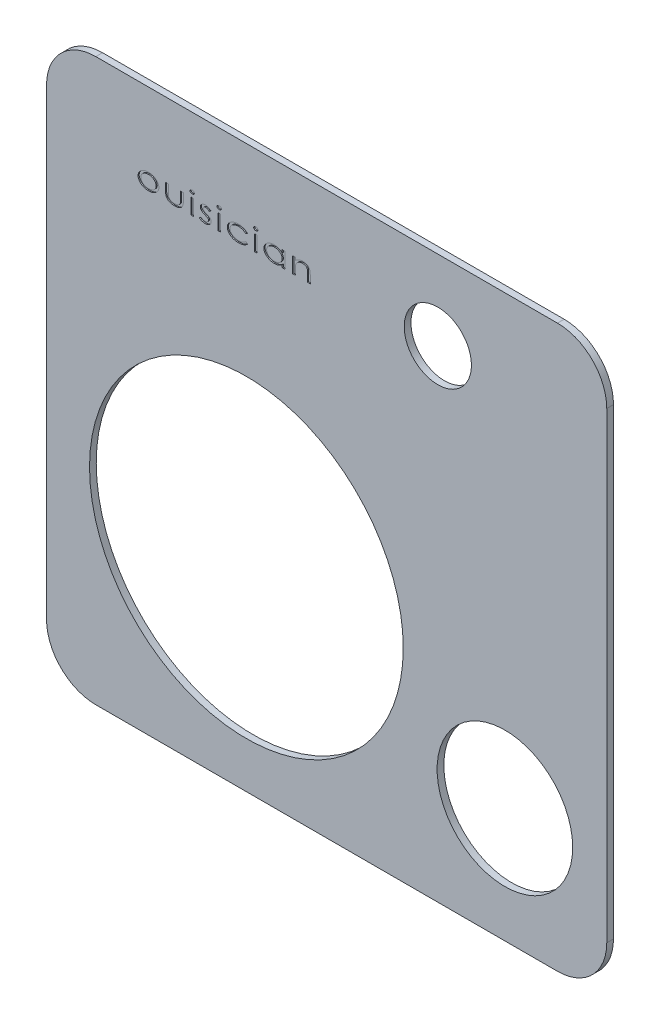
SolidWorks part; units mm, degrees
material "Pine"
ref_plane "Front Plane" through (0, 0, 0) normal (0, 0, 1) x (1, 0, 0)
ref_plane "Top Plane" through (0, 0, 0) normal (0, 1, 0) x (1, 0, 0)
ref_plane "Right Plane" through (0, 0, 0) normal (1, 0, 0) x (0, 0, -1)
sketch "Sketch1" plane through (0, 0, 0) normal (0, 0, 1) x (1, 0, 0)
  line L1 (0, 0) -> (500, 0)
  line L2 (0, 0) -> (0, 501)
  line L3 (0, 501) -> (500, 501)
  line L4 (500, 0) -> (500, 501)
  dimension "D1" = 500
  dimension "D2" = 501
extrude "Boss-Extrude1" add sketch "Sketch1" along normal blind 6
fillet "Fillet1" radius 44 4 edges at (0, 0, 3) (500, 0, 3) (0, 501, 3) (500, 501, 3)
sketch "Sketch2" plane through (0, 0, 6) normal (0, 0, 1) x (1, 0, 0)
  circle A0 centre (178.369, 181.0347) radius 156
  dimension "D1" = 312
sketch "Sketch3" plane through (0, 0, 6) normal (0, 0, 1) x (1, 0, 0)
  circle A1 centre (178.369, 181.0347) radius 140
  dimension "D1" = 280
extrude "Cut-Extrude2" cut sketch "Sketch3" against normal through all
sketch "Sketch4" plane through (0, 0, 6) normal (0, 0, 1) x (1, 0, 0)
  circle A0 centre (409.1034, 102.5162) radius 72.5
  dimension "D1" = 145
sketch "Sketch5" plane through (0, 0, 6) normal (0, 0, 1) x (1, 0, 0)
  circle A0 centre (409.1034, 102.5162) radius 60.5
  dimension "D1" = 121
extrude "Cut-Extrude3" cut sketch "Sketch5" against normal through all
sketch "Sketch6" plane through (0, 0, 6) normal (0, 0, 1) x (1, 0, 0)
  line L0 (500, 360) -> (0, 360)
  line L1 (500, 44) -> (500, 457) construction
  line L2 (0, 457) -> (0, 44) construction
  line L3 (44, 0) -> (456, 0) construction
  line L4 (456, 501) -> (44, 501) construction
  circle A0 centre (349.2286, 430) radius 50
  circle A1 centre (349.2286, 430) radius 30
  dimension "D1" = 100
  dimension "D3" = 60
  dimension "D2" = 360
  dimension "D4" = 71
extrude "Cut-Extrude5" cut sketch "Sketch6" against normal through all contours A1 region at (349.2286, 430, 6)
sketch "Sketch7" plane through (0, 0, 6) normal (0, 0, 1) x (1, 0, 0)
  line L0 (0, 457) -> (0, 44) construction
  line L1 (456, 501) -> (44, 501) construction
  text T0 "ouisician" font "Century Gothic" height in points 72
  dimension "D1" = 80
  dimension "D2" = 80
sketch "Sketch10" plane through (0, 0, 6) normal (0, 0, 1) x (1, 0, 0)
  line L0 (0, 366) -> (500, 366)
  line L1 (0, 457) -> (0, 44) construction
  line L2 (500, 44) -> (500, 457) construction
  line L3 (456, 501) -> (44, 501) construction
  line L4 (0, 360) -> (500, 360)
  line L5 (44, 0) -> (456, 0) construction
  dimension "D1" = 500
  dimension "D2" = 135
  dimension "D3" = 360
extrude "Cut-Extrude6" cut sketch "Sketch7" against normal blind 1
